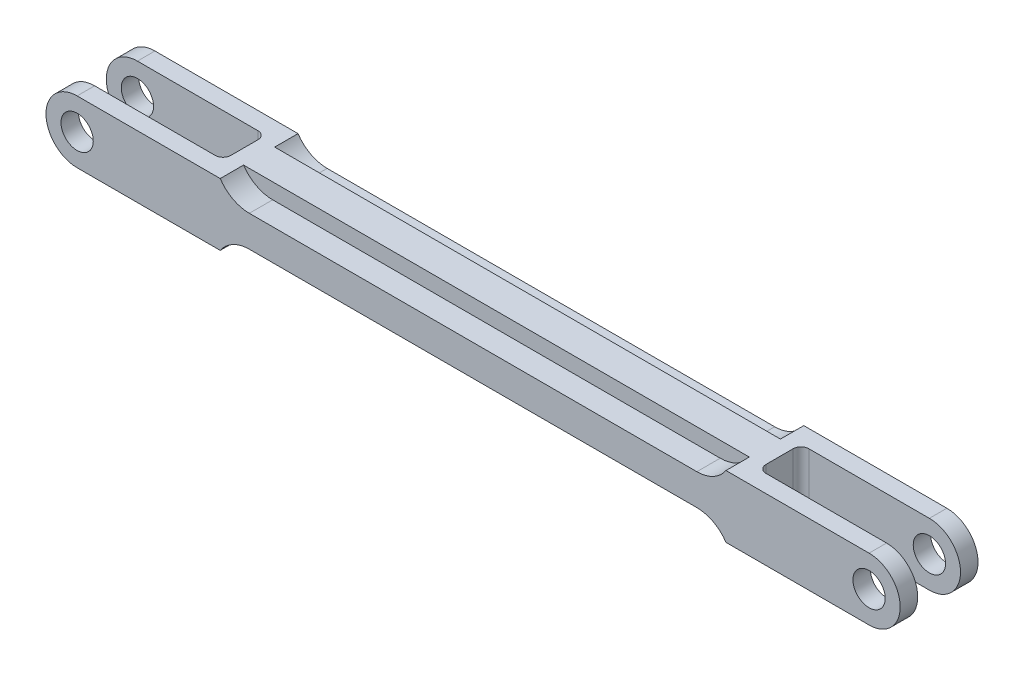
SolidWorks part; units mm, degrees
ref_plane "Plano frontal" through (0, 0, 0) normal (0, 0, 1) x (1, 0, 0)
ref_plane "Plano superior" through (0, 0, 0) normal (0, 1, 0) x (1, 0, 0)
ref_plane "Plano direito" through (0, 0, 0) normal (1, 0, 0) x (0, 0, -1)
sketch "Esboço1" plane through (0, 0, 0) normal (0, 0, 1) x (1, 0, 0)
  line L0 (208.8814, 163) -> (412.4421, 163)
  line L1 (208.8814, 147) -> (412.4421, 147)
  circle A0 centre (208.8814, 155) radius 4.15
  circle A1 centre (412.4421, 155) radius 4.15
  arc A2 (208.8814, 163) -> (208.8814, 147) centre (208.8814, 155) ccw
  arc A3 (412.4421, 147) -> (412.4421, 163) centre (412.4421, 155) ccw
  dimension "D1" = 8
  dimension "D2" = 8.3
extrude "Ressalto-extrusão1" add sketch "Esboço1" along normal mid plane 20
sketch "Esboço2" plane through (0, 163, 0) normal (0, 1, 0) x (1, 0, 0)
  line L0 (200.8814, 10) -> (200.8814, -10) construction
  line L1 (200.8814, 5.5) -> (241.8814, 5.5)
  line L2 (200.8814, 5.5) -> (200.8814, -5.5)
  line L3 (200.8814, -5.5) -> (241.8814, -5.5)
  line L4 (241.8814, 5.5) -> (241.8814, -5.5)
  line L5 (198.8814, -5) -> (202.0067, -5) construction
  line L6 (216.8814, 5) -> (200.8814, 5) construction
  line L7 (216.8814, -5) -> (216.8814, 5) construction
  dimension "D1" = 0.5
  dimension "D2" = 0.5
  dimension "D3" = 25
extrude "Corte-extrusão1" cut sketch "Esboço2" against normal through all
fillet "Filete1" radius 2 2 edges at (241.8814, 155, -5.5) (241.8814, 155, 5.5)
sketch "Esboço3" plane through (0, 163, 0) normal (0, 1, 0) x (1, 0, 0)
  line L0 (420.4421, -10) -> (420.4421, 10) construction
  line L1 (420.4421, 5.5) -> (379.4421, 5.5)
  line L2 (420.4421, 5.5) -> (420.4421, -5.5)
  line L3 (420.4421, -5.5) -> (379.4421, -5.5)
  line L4 (379.4421, 5.5) -> (379.4421, -5.5)
  line L5 (404.4421, -5) -> (420.4421, -5) construction
  dimension "D1" = 0.5
  dimension "D2" = 41
extrude "Corte-extrusão2" cut sketch "Esboço3" against normal through all
sketch "Esboço4" plane through (0, 0, 10) normal (0, 0, 1) x (1, 0, 0)
  line L0 (412.4421, 163) -> (208.8814, 163) construction
  line L1 (245.6618, 124.2164) -> (375.6618, 124.2164)
  line L2 (245.6618, 124.2164) -> (245.6618, 175.5503)
  line L3 (245.6618, 175.5503) -> (375.6618, 175.5503)
  line L4 (375.6618, 124.2164) -> (375.6618, 175.5503)
  line L5 (245.6618, 124.2164) -> (375.6618, 175.5503) construction
  line L6 (245.6618, 175.5503) -> (375.6618, 124.2164) construction
  point P0 (310.6618, 149.8833)
  point P7 (310.6618, 163)
  dimension "D1" = 130
extrude "Corte-extrusão3" cut sketch "Esboço4" against normal through all
sketch "Esboço5" plane through (245.6618, 0, 0) normal (1, 0, 0) x (0, 0, -1)
  line L0 (-10, 163) -> (10, 163) construction
  line L2 (-4, 147) -> (-4, 151)
  line L4 (4, 147) -> (4, 151)
  line L5 (-13.3177, 150.4058) -> (4, 156.3799) construction
  line L6 (-4, 156.3799) -> (13.3177, 150.4058) construction
  line L7 (-10, 163) -> (-10, 147) construction
  line L8 (-10, 159) -> (-4, 159)
  line L10 (-10, 151) -> (-4, 151)
  line L12 (-3.1116, 158.1009) -> (12.1726, 148.8403) construction
  line L13 (-13.892, 141) -> (7.0813, 155.0111) construction
  line L14 (-4, 159) -> (-4, 163)
  line L15 (4, 151) -> (10, 151)
  line L16 (4, 159) -> (4, 163)
  line L17 (4, 159) -> (10, 159)
  line L18 (10, 163) -> (10, 147) construction
  line L19 (-10, 159) -> (-10, 151)
  line L20 (10, 159) -> (10, 151)
  line L21 (-4, 163) -> (4, 163)
  line L22 (10, 147) -> (-10, 147) construction
  line L23 (4, 147) -> (-4, 147)
  point P0 (0, 155)
  point P7 (0, 163)
  point P8 (4.6588, 153.3928)
  point P29 (10, 155)
  dimension "D1" = 8
  dimension "D2" = 8
  dimension "D3" = 4
  dimension "D4" = 4
  dimension "D5" = 4
  dimension "D6" = 4
  dimension "D7" = 4
extrude "Ressalto-extrusão2" add sketch "Esboço5" along normal up to surface (130 mm away) up to face at (375.6618, 155, 0)
fillet "Filete2" radius 9 8 edges at (375.6618, 151, -7) (375.6618, 151, 7) (375.6618, 159, 7) (375.6618, 159, -7) (245.6618, 151, -7) (245.6618, 151, 7) (245.6618, 159, -7) (245.6618, 159, 7)
ref_plane "Plano1" through (0, 155, 0) normal (0, 1, 0) x (1, 0, 0)
fillet "Filete3" radius 2 2 edges at (379.4421, 155, 5.5) (379.4421, 155, -5.5)
